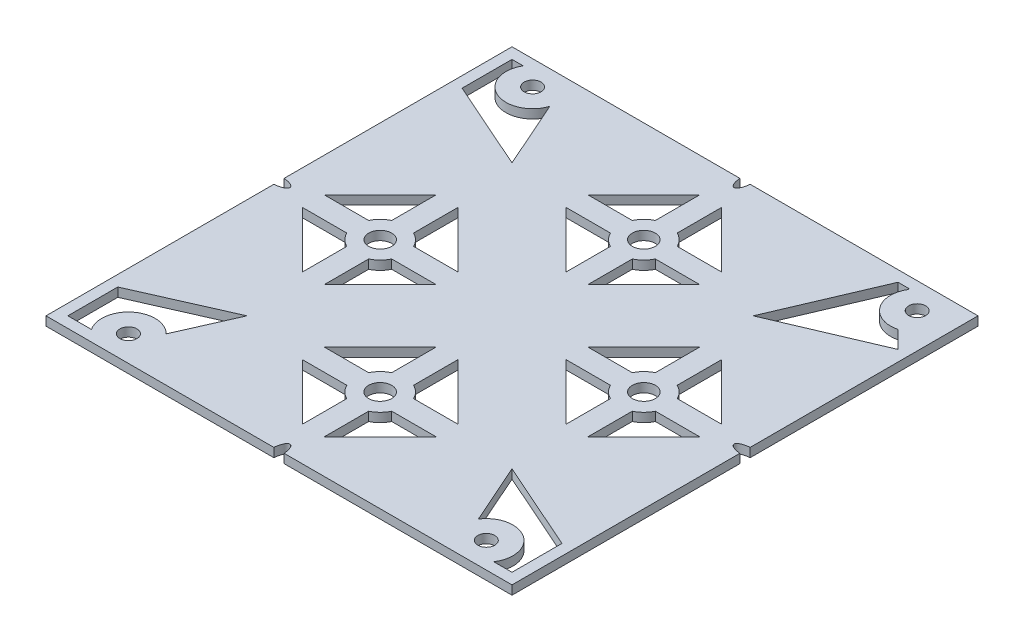
SolidWorks part; units mm, degrees
material "ABS"
ref_plane "Front Plane" through (0, 0, 0) normal (0, 0, 1) x (1, 0, 0)
ref_plane "Top Plane" through (0, 0, 0) normal (0, 1, 0) x (1, 0, 0)
ref_plane "Right Plane" through (0, 0, 0) normal (1, 0, 0) x (0, 0, -1)
sketch "Sketch1" plane through (0, 0, 0) normal (0, 1, 0) x (1, 0, 0)
  line L1 (0, 0) -> (97.6, 0)
  line L2 (0, 0) -> (0, 97.6)
  line L3 (0, 97.6) -> (97.6, 97.6)
  line L4 (97.6, 0) -> (97.6, 97.6)
  dimension "D1" = 97.6
  dimension "D2" = 97.6
extrude "Boss-Extrude1" add sketch "Sketch1" along normal blind 1.85
sketch "Sketch2" plane through (0, 0, 0) normal (0, -1, 0) x (-1, 0, 0)
  line L0 (-97.6, 97.6) -> (0, 0) construction
  line L1 (-97.6, 0) -> (0, 97.6) construction
  line L2 (-48.8, 97.6) -> (-48.8, 0) construction
  line L3 (-97.6, 97.6) -> (0, 97.6) construction
  line L4 (0, 0) -> (-97.6, 0) construction
  line L5 (-97.6, 48.8) -> (0, 48.8) construction
  line L6 (-97.6, 0) -> (-97.6, 97.6) construction
  line L7 (0, 97.6) -> (0, 0) construction
sketch "Sketch3" plane through (0, 0, 0) normal (0, -1, 0) x (1, 0, 0)
  line L0 (97.6, -97.6) -> (0, -97.6) construction
  line L1 (97.6, 0) -> (97.6, -97.6) construction
  line L2 (0, -97.6) -> (0, 0) construction
  line L3 (0, 0) -> (97.6, 0) construction
  line L4 (97.6, -94.6) -> (0, -94.6) construction
  line L5 (3, -97.6) -> (3, 0) construction
  line L6 (3, -94.6) -> (5.3161, -94.6)
  line L7 (3, -94.6) -> (3, -84.3)
  line L8 (3, -84.3) -> (21.4728, -76.1272)
  line L9 (97.6, 0) -> (0, -97.6) construction
  line L10 (21.4728, -76.1272) -> (13.3, -94.6)
  line L11 (21.4728, -21.4728) -> (13.3, -3)
  line L12 (3, -3) -> (13.3, -3)
  line L13 (0, -3) -> (97.6, -3) construction
  line L14 (3, -13.3) -> (3, -3)
  line L15 (3, -3) -> (7.8732, -3)
  line L16 (3, -13.3) -> (21.4728, -21.4728)
  line L17 (97.6, -97.6) -> (0, 0) construction
  line L18 (0, -97.6) -> (0, 0) construction
  line L19 (16.1614, -10.109) -> (21.4728, -21.4728) construction
  line L20 (94.6, -97.6) -> (94.6, 0) construction
  line L21 (94.6, -3) -> (94.6, -13.3)
  line L22 (94.6, -3) -> (84.3, -3)
  line L23 (94.6, -13.3) -> (76.1272, -21.4728)
  line L24 (76.1272, -21.4728) -> (84.3, -3)
  line L25 (94.6, -82.6) -> (73.6741, -73.6741)
  line L26 (73.6741, -73.6741) -> (82.6, -94.6)
  line L27 (94.6, -82.6) -> (82.6, -94.6) construction
  line L28 (94.6, -82.6) -> (91.0273, -86.1727)
  line L29 (82.6, -94.6) -> (85.1169, -94.6)
  line L30 (3, -94.6) -> (13.3, -94.6) construction
  circle A0 centre (89.66, -91.5) radius 1.25
  circle A1 centre (10.05, -91.8) radius 1.25
  circle A2 centre (12.45, -6.05) radius 1.25
  circle A3 centre (86.25, -6.05) radius 1.25
  circle A4 centre (89.66, -91.5) radius 5.5
  circle A5 centre (10.05, -91.8) radius 5.5
  circle A6 centre (12.45, -6.05) radius 5.5
  circle A7 centre (86.25, -6.05) radius 5.5
  dimension "D1" = 6.1
  dimension "D9" = 3
  dimension "D16" = 3
  dimension "D20" = 2.5
  dimension "D21" = 11
  dimension "D23" = 11
  dimension "D24" = 2.5
  dimension "D26" = 11
  dimension "D27" = 11
  dimension "D2" = 7.94
  dimension "D3" = 5.8
  dimension "D4" = 10.05
  dimension "D5" = 6.05
  dimension "D6" = 12.45
  dimension "D7" = 6.05
  dimension "D8" = 11.35
  dimension "D10" = 3
  dimension "D11" = 10.3
  dimension "D12" = 20.2
  dimension "D13" = 3
  dimension "D14" = 10.3
  dimension "D15" = 20.2
  dimension "D17" = 10.3
  dimension "D18" = 22.75
  dimension "D19" = 15
  dimension "D22" = 10.3
  dimension "D25" = 20.2
extrude "Cut-Extrude1" cut sketch "Sketch3" against normal blind 10 contours A2 | A1 | A1 | A5 L8 L7 L6 | A4 L28 L25 L26 L29 | A3 | A7 L24 L23 L21 L22 | A6 L15 L14 L16 | A0 region at (11.5662, 0, -84.2704) region at (10.6634, 0, -12.5774) region at (86.5986, 0, -12.9459) region at (83.266, 0, -83.1897) region at (10.05, 0, -91.8) region at (12.45, 0, -6.05) region at (86.25, 0, -6.05)
fillet "Fillet1" radius 0.2 1 edges at (85.1169, 0.925, -94.6)
sketch "Sketch5" plane through (0, 0, 0) normal (0, -1, 0) x (1, 0, 0)
  line L0 (78.0601, -69.3344) -> (24.4532, -15.7275) construction
  line L1 (15.9101, -24.6358) -> (67.2589, -75.9846) construction
  line L2 (97.6, -97.6) -> (0, 0) construction
  line L3 (25.594, -80.7317) -> (80.9701, -25.3556) construction
  line L4 (71.5743, -17.3) -> (16.8047, -72.0696) construction
  line L5 (97.6, 0) -> (0, -97.6) construction
  line L6 (51.05, -89.7671) -> (51.05, -80.6171)
  line L7 (46.55, -89.7671) -> (46.55, -80.6171)
  line L8 (48.8, -97.6) -> (48.8, 0) construction
  line L9 (51.05, -89.7671) -> (62.5825, -78.2346)
  line L10 (62.5825, -78.2346) -> (53.4325, -78.2346)
  line L11 (44.1675, -78.2346) -> (35.0175, -78.2346)
  line L12 (35.0175, -78.2346) -> (46.55, -89.7671)
  line L13 (48.8, -78.2346) -> (36.0473, -78.2346) construction
  line L14 (48.8, -73.7346) -> (36.0473, -73.7346) construction
  line L15 (44.1675, -73.7346) -> (35.0175, -73.7346)
  line L16 (46.55, -71.3521) -> (46.55, -62.2021)
  line L17 (53.4325, -73.7346) -> (62.5825, -73.7346)
  line L18 (51.05, -71.3521) -> (51.05, -62.2021)
  line L19 (62.5825, -73.7346) -> (51.05, -62.2021)
  line L20 (46.55, -62.2021) -> (35.0175, -73.7346)
  line L21 (48.8, -48.8) -> (-2.5605, -100.1605) construction
  line L22 (48.8, -48.8) -> (97.6, 0) construction
  line L23 (97.6, -97.6) -> (0, 0) construction
  line L24 (73.7346, -48.8) -> (73.7346, -36.0473) construction
  line L25 (78.2346, -48.8) -> (78.2346, -36.0473) construction
  line L26 (62.2021, -46.55) -> (73.7346, -35.0175)
  line L27 (73.7346, -62.5825) -> (62.2021, -51.05)
  line L28 (71.3521, -51.05) -> (62.2021, -51.05)
  line L29 (73.7346, -53.4325) -> (73.7346, -62.5825)
  line L30 (71.3521, -46.55) -> (62.2021, -46.55)
  line L31 (73.7346, -44.1675) -> (73.7346, -35.0175)
  line L32 (78.2346, -35.0175) -> (89.7671, -46.55)
  line L33 (78.2346, -44.1675) -> (78.2346, -35.0175)
  line L34 (78.2346, -62.5825) -> (78.2346, -53.4325)
  line L35 (89.7671, -51.05) -> (78.2346, -62.5825)
  line L36 (89.7671, -46.55) -> (80.6171, -46.55)
  line L37 (89.7671, -51.05) -> (80.6171, -51.05)
  line L38 (48.8, -19.3654) -> (61.5527, -19.3654) construction
  line L39 (48.8, -23.8654) -> (61.5527, -23.8654) construction
  line L40 (23.8654, -48.8) -> (23.8654, -61.5527) construction
  line L41 (19.3654, -48.8) -> (19.3654, -61.5527) construction
  line L42 (46.55, -7.8329) -> (46.55, -16.9829)
  line L43 (51.05, -7.8329) -> (51.05, -16.9829)
  line L44 (46.55, -7.8329) -> (35.0175, -19.3654)
  line L45 (35.0175, -19.3654) -> (44.1675, -19.3654)
  line L46 (53.4325, -19.3654) -> (62.5825, -19.3654)
  line L47 (62.5825, -19.3654) -> (51.05, -7.8329)
  line L48 (53.4325, -23.8654) -> (62.5825, -23.8654)
  line L49 (51.05, -26.2479) -> (51.05, -35.3979)
  line L50 (44.1675, -23.8654) -> (35.0175, -23.8654)
  line L51 (46.55, -26.2479) -> (46.55, -35.3979)
  line L52 (35.0175, -23.8654) -> (46.55, -35.3979)
  line L53 (51.05, -35.3979) -> (62.5825, -23.8654)
  line L54 (35.3979, -51.05) -> (23.8654, -62.5825)
  line L55 (23.8654, -35.0175) -> (35.3979, -46.55)
  line L56 (26.2479, -46.55) -> (35.3979, -46.55)
  line L57 (23.8654, -44.1675) -> (23.8654, -35.0175)
  line L58 (26.2479, -51.05) -> (35.3979, -51.05)
  line L59 (23.8654, -53.4325) -> (23.8654, -62.5825)
  line L60 (19.3654, -62.5825) -> (7.8329, -51.05)
  line L61 (19.3654, -53.4325) -> (19.3654, -62.5825)
  line L62 (19.3654, -35.0175) -> (19.3654, -44.1675)
  line L63 (7.8329, -46.55) -> (19.3654, -35.0175)
  line L64 (7.8329, -51.05) -> (16.9829, -51.05)
  line L65 (7.8329, -46.55) -> (16.9829, -46.55)
  line L66 (49.9, -97.6) -> (47.7, -97.6)
  line L67 (97.6, -97.6) -> (0, -97.6) construction
  line L68 (97.6, -48.8) -> (97.6, -49.9)
  line L69 (97.6, 0) -> (97.6, -97.6) construction
  line L70 (97.6, -48.8) -> (97.6, -47.7)
  line L71 (0, -49.9) -> (0, -48.8)
  line L72 (0, -97.6) -> (0, 0) construction
  line L73 (0, -48.8) -> (0, -47.7)
  line L74 (48.8, 0) -> (49.9, 0)
  line L75 (0, 0) -> (97.6, 0) construction
  line L76 (48.8, 0) -> (47.7, 0)
  circle A0 centre (48.8, -75.9846) radius 2.375
  circle A1 centre (48.8, -75.9846) radius 5.15
  circle A2 centre (75.9846, -48.8) radius 5.15
  circle A3 centre (75.9846, -48.8) radius 2.375
  circle A4 centre (48.8, -21.6154) radius 2.375
  circle A5 centre (48.8, -21.6154) radius 5.15
  circle A6 centre (21.6154, -48.8) radius 5.15
  circle A7 centre (21.6154, -48.8) radius 2.375
  ellipse E0 centre (48.8, -97.6) end of major axis (48.8, -94.6046) minor radius 1.1
  ellipse E1 centre (97.6, -48.8) end of major axis (94.5962, -48.8) minor radius 1.1
  ellipse E2 centre (0, -48.8) end of major axis (3, -48.8) minor radius 1.1
  ellipse E3 centre (48.8, 0) end of major axis (48.8, -3) minor radius 1.1
  line M15 (0, 0) -> (0, -97.6)
  line M16 (0, -97.6) -> (97.6, -97.6)
  line M17 (97.6, -97.6) -> (97.6, 0)
  line M18 (97.6, 0) -> (0, 0)
  dimension "D5" = 9.15
  dimension "D7" = 4.75
  dimension "D8" = 10.3
  dimension "D1" = 6.17
  dimension "D2" = 6.17
  dimension "D3" = 6.17
  dimension "D4" = 6.17
  dimension "D6" = 2.25
  dimension "D9" = 2.25
  dimension "D10" = 1.1
  dimension "D11" = 1.1
  dimension "D12" = 1.1
  dimension "D13" = 3
  dimension "D14" = 2.25
  dimension "D15" = 2.25
  dimension "D16" = 3
extrude "Cut-Extrude2" cut sketch "Sketch5" against normal blind 10 contours A1 L6 L9 L10 | A1 L11 L12 L7 | A0 | A1 L17 L19 L18 | A1 L16 L20 L15 | L61 A6 L64 L60 | L58 A6 L59 L54 | L57 A6 L56 L55 | L65 A6 L62 L63 | A7 | A3 | L37 A2 L34 L35 | L29 A2 L28 L27 | L30 A2 L31 L26 | L33 A2 L36 L32 | A5 L42 L44 L45 | A5 L46 L47 L43 | A5 L49 L53 L48 | A5 L50 L52 L51 | E0 M16 | E3 M18 | E1 M17 | E2 M15 | A4 region at (55.0576, 0, -82.2422) region at (42.5424, 0, -82.2422) region at (42.5424, 0, -69.7269) region at (55.0576, 0, -69.7269) region at (69.7269, 0, -42.5424) region at (69.7269, 0, -55.0576) region at (82.2422, 0, -42.5424) region at (82.2422, 0, -55.0576) region at (42.5424, 0, -15.3578) region at (55.0576, 0, -15.3578) region at (42.5424, 0, -27.8731) region at (55.0576, 0, -27.8731) region at (27.8731, 0, -55.0576) region at (15.3578, 0, -55.0576) region at (27.8731, 0, -42.5424) region at (15.3578, 0, -42.5424) region at (48.8, 0, -96.3287) region at (96.3251, 0, -48.8) region at (1.2732, 0, -48.8) region at (48.8, 0, -1.2732) region at (48.8, 0, -75.9846) region at (75.9846, 0, -48.8) region at (21.6154, 0, -48.8)
sketch "Sketch6" plane through (0, 0, 0) normal (0, -1, 0) x (1, 0, 0)
  circle A0 centre (12.45, -6.05) radius 1.75
  circle A1 centre (86.25, -6.05) radius 1.75
  circle A2 centre (10.05, -91.8) radius 1.75
  circle A3 centre (89.66, -91.5) radius 1.75
  dimension "D1" = 3.5
  dimension "D2" = 3.5
  dimension "D3" = 3.5
  dimension "D4" = 3.5
extrude "Cut-Extrude3" cut sketch "Sketch6" against normal through all
sketch "Sketch7" plane through (0, 0, -97.6) normal (0, 0, -1) x (-1, 0, 0)
  line L1 (0, 0) -> (-97.6, 0)
  line L2 (0, 0) -> (0, 1.85)
  line L3 (0, 1.85) -> (-97.6, 1.85)
  line L4 (-97.6, 0) -> (-97.6, 1.85)
extrude "Cut-Extrude4" cut sketch "Sketch7" against normal blind 0.75
sketch "Sketch8" plane through (97.6, 0, 0) normal (1, 0, 0) x (0, 0, -1)
  line L1 (96.85, 0) -> (0, 0)
  line L2 (96.85, 0) -> (96.85, 1.85)
  line L3 (96.85, 1.85) -> (0, 1.85)
  line L4 (0, 0) -> (0, 1.85)
extrude "Cut-Extrude5" cut sketch "Sketch8" against normal blind 0.75
sketch "Sketch9" plane through (0, 0, 0) normal (0, 0, 1) x (1, 0, 0)
  line L1 (0, 0) -> (96.85, 0)
  line L2 (0, 0) -> (0, 1.85)
  line L3 (0, 1.85) -> (96.85, 1.85)
  line L4 (96.85, 0) -> (96.85, 1.85)
extrude "Cut-Extrude6" cut sketch "Sketch9" against normal blind 0.75
sketch "Sketch12" plane through (0, 0, 0) normal (-1, 0, 0) x (0, 0, 1)
  line L1 (-0.75, 0) -> (-96.85, 0)
  line L2 (-0.75, 0) -> (-0.75, 1.85)
  line L3 (-0.75, 1.85) -> (-96.85, 1.85)
  line L4 (-96.85, 0) -> (-96.85, 1.85)
extrude "Cut-Extrude7" cut sketch "Sketch12" against normal blind 0.75
